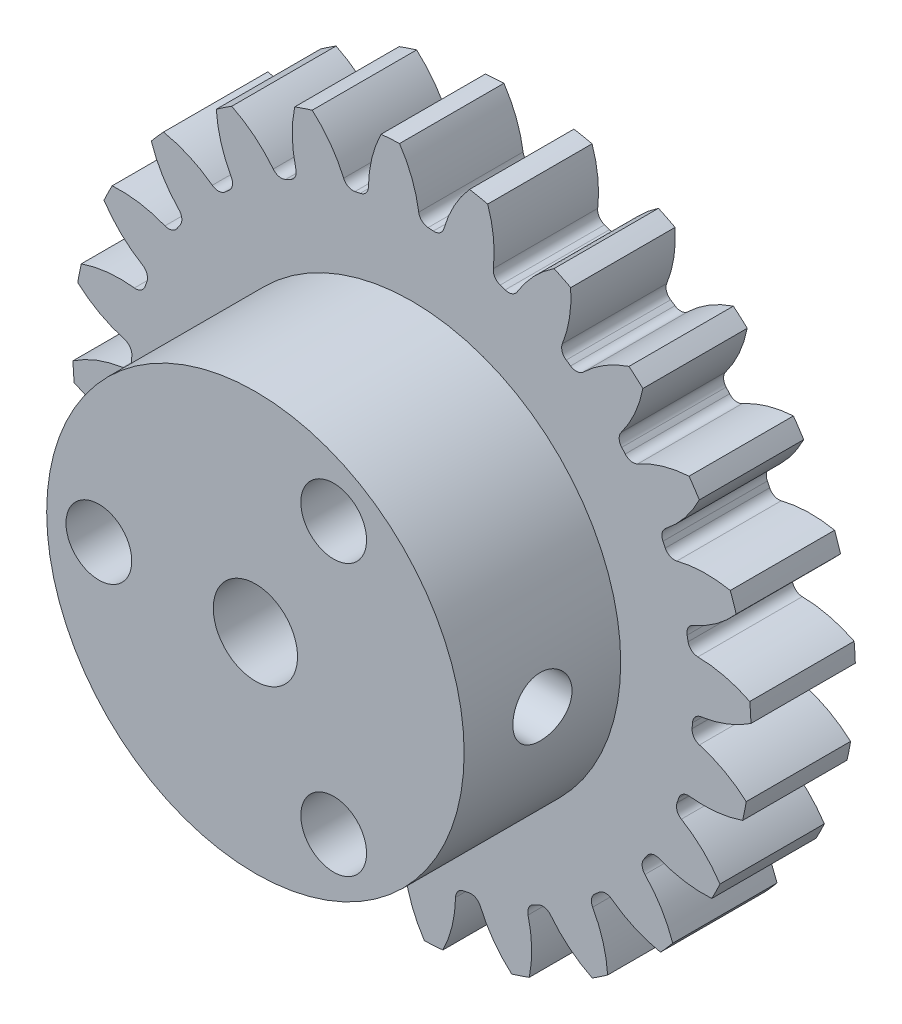
SolidWorks part; units mm, degrees
ref_plane "Front" through (0, 0, 0) normal (0, 0, 1) x (1, 0, 0)
ref_plane "Top" through (0, 0, 0) normal (0, 1, 0) x (1, 0, 0)
ref_plane "Right" through (0, 0, 0) normal (1, 0, 0) x (0, 0, -1)
sketch "Sketch3" plane through (0, 0, 0) normal (0, 0, 1) x (1, 0, 0)
  circle A0 centre (0, 0) radius 20.6375
  dimension "od" = 41.275
extrude "gearBody" add sketch "Sketch3" along normal blind 6.35
sketch "Sketch2" plane through (0, 0, 0) normal (0, 0, 1) x (1, 0, 0)
  line L0 (0, 0) -> (16.5385, 6.8505) construction
  line L1 (22.0347, -5.709) -> (0, 0) construction
  line L2 (0, 0) -> (36.3143, 0) construction
  line L3 (19.05, -0.043) -> (18.8852, -2.5004) construction
  line L5 (18.9676, -1.2717) -> (0, 0) construction
  line L7 (0, 0) -> (17.9011, 0) construction
  arc A0 (17.8975, -0.3593) -> (17.7853, -2.0332) centre (0, 0) ccw construction
  arc A1 (20.6236, 0.7563) -> (20.3381, -3.5027) centre (0, 0) ccw construction
  arc A2 (19.05, -0.043) -> (18.8852, -2.5004) centre (0, 0) ccw construction
  arc A3 (17.0444, -1.304) -> (17.0659, -0.983) centre (0, 0) ccw
  arc A4 (22.0347, -5.709) -> (17.4884, -1.9416) centre (15.476, -8.9969) ccw
  arc A5 (22.0347, -5.709) -> (22.5996, 2.7164) centre (0, 0) ccw
  arc A6 (22.5996, 2.7164) -> (17.5911, -0.4103) centre (16.5385, 6.8505) cw
  arc A7 (17.0659, -0.983) -> (17.5911, -0.4103) centre (17.6793, -1.0183) cw
  arc A8 (17.4884, -1.9416) -> (17.0444, -1.304) centre (17.657, -1.3509) cw
  point P6 (22.5996, 2.7164)
  point P22 (22.0347, -5.709)
  dimension "baseDia" = 35.8023
  dimension "od" = 41.275
  dimension "pd" = 38.1
  dimension "rd" = 34.1884
  dimension "rFillet" = 0.6144
  dimension "pointX" = 22.5996
  dimension "pointY" = 2.7164
  dimension "CTT" = 2.4574
  dimension "flankCenterAngle" = 22.5
extrude "toothCut" cut sketch "Sketch2" along normal through all
pattern_circular "CirPattern1" count 24 over 360 about axis through (0, 0, 6.35) along (0, 0, -1) of "toothCut"
sketch "hub1Dia" plane through (0, 0, 0) normal (0, 0, -1) x (-1, 0, 0)
  circle A0 centre (0, 0) radius 12.7
  dimension "hub1Dia" = 25.4
sketch "hub2Dia" plane through (0, 0, 6.35) normal (0, 0, 1) x (1, 0, 0)
  circle A0 centre (0, 0) radius 12.7
  dimension "hub2dia" = 25.4
sketch "boreDia" plane through (0, 0, 0) normal (0, 0, 1) x (1, 0, 0)
  circle A0 centre (0, 0) radius 6.35
  dimension "boreDia" = 12.7
extrude "Boss-Extrude1" add sketch "hub2Dia" along normal blind 9.525
sketch "Sketch4" plane through (0, 0, 0) normal (0, 0, -1) x (-1, 0, 0)
  circle A0 centre (9.525, 0) radius 2
  circle A1 centre (-4.7625, -8.2489) radius 2
  circle A2 centre (-4.7625, 8.2489) radius 2
  point P9 (0, 0)
  dimension "D2" = 4
  dimension "D1" = 9.525
  dimension "D3" = 3
extrude "Cut-Extrude1" cut sketch "Sketch4" against normal through all
sketch "Sketch5" plane through (0, 0, 0) normal (0, 0, -1) x (-1, 0, 0)
  circle A0 centre (0, 0) radius 2.5635
  dimension "D1" = 5.127
extrude "Cut-Extrude2" cut sketch "Sketch5" against normal through all
sketch "Sketch6" plane through (0, 0, 0) normal (1, 0, 0) x (0, 0, -1)
  line L0 (-15.875, 12.7) -> (-15.875, -12.7) construction
  circle A0 centre (-11.1125, 0) radius 1.8
  dimension "D2" = 3.6
  dimension "D1" = 4.7625
extrude "Cut-Extrude3" cut sketch "Sketch6" along normal through all
equation "\"D2@Sketch4\"=4mm"
equation "\"D1@Sketch5\"=\"tightTol\" + 5mm"
equation "\"tightTol\" = 0.005in"
equation "\"normTol\"= 0.01in"
equation "\"looseTol\"= 0.02in"
equation "\"D2@Sketch6\"=3.6mm"
